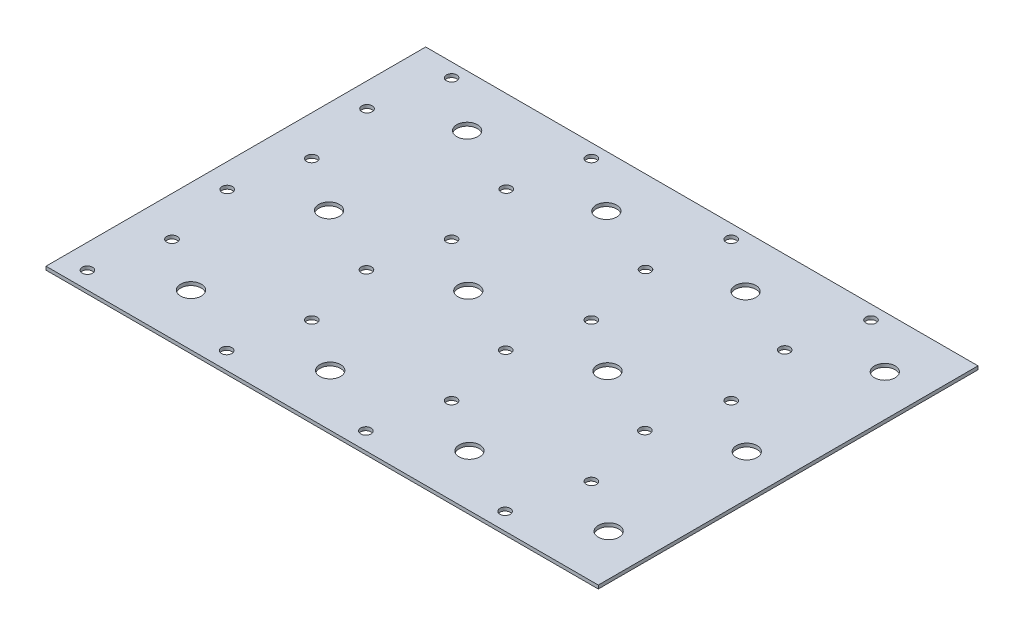
SolidWorks part; units mm, degrees
ref_plane "Front Plane" through (0, 0, 0) normal (0, 0, 1) x (1, 0, 0)
ref_plane "Top Plane" through (0, 0, 0) normal (0, 1, 0) x (1, 0, 0)
ref_plane "Right Plane" through (0, 0, 0) normal (1, 0, 0) x (0, 0, -1)
sketch "Sketch1" plane through (0, 0, 0) normal (0, 1, 0) x (1, 0, 0)
  line L1 (-80, -55) -> (80, -55)
  line L2 (-80, -55) -> (-80, 55)
  line L3 (-80, 55) -> (80, 55)
  line L4 (80, -55) -> (80, 55)
  line L5 (-80, -55) -> (80, 55) construction
  line L6 (-80, 55) -> (80, -55) construction
  point P0 (0, 0)
  dimension "D1" = 160
  dimension "D2" = 110
extrude "Boss-Extrude1" add sketch "Sketch1" along normal blind 1
sketch "Sketch2" plane through (0, 1, 0) normal (0, 1, 0) x (1, 0, 0)
  line L0 (-80, 55) -> (-80, -55) construction
  line L1 (80, 55) -> (-80, 55) construction
  line L2 (80, -55) -> (80, 55) construction
  line L3 (-80, -55) -> (80, -55) construction
  circle A0 centre (-53, 40) radius 3
  circle A1 centre (-12.6667, 40) radius 3
  circle A2 centre (27.6667, 40) radius 3
  circle A3 centre (68, 40) radius 3
  circle A4 centre (-12.6667, 0) radius 3
  circle A5 centre (27.6667, 0) radius 3
  circle A6 centre (68, 0) radius 3
  circle A7 centre (-12.6667, -40) radius 3
  circle A8 centre (27.6667, -40) radius 3
  circle A9 centre (68, -40) radius 3
  circle A10 centre (-53, 0) radius 3
  circle A11 centre (-53, -40) radius 3
  circle A12 centre (-68.5, 51) radius 1.5
  circle A13 centre (-28, 51) radius 1.5
  circle A14 centre (12.5, 51) radius 1.5
  circle A15 centre (53, 51) radius 1.5
  circle A16 centre (-28, 10.5) radius 1.5
  circle A17 centre (12.5, 10.5) radius 1.5
  circle A18 centre (53, 10.5) radius 1.5
  circle A19 centre (-28, -30) radius 1.5
  circle A20 centre (12.5, -30) radius 1.5
  circle A21 centre (53, -30) radius 1.5
  circle A22 centre (-68.5, 10.5) radius 1.5
  circle A23 centre (-68.5, -30) radius 1.5
  circle A24 centre (-73, 31) radius 1.5
  circle A25 centre (-32.6667, 31) radius 1.5
  circle A26 centre (7.6667, 31) radius 1.5
  circle A27 centre (48, 31) radius 1.5
  circle A28 centre (-32.6667, -9.5) radius 1.5
  circle A29 centre (7.6667, -9.5) radius 1.5
  circle A30 centre (48, -9.5) radius 1.5
  circle A31 centre (-32.6667, -50) radius 1.5
  circle A32 centre (7.6667, -50) radius 1.5
  circle A33 centre (48, -50) radius 1.5
  circle A34 centre (-73, -9.5) radius 1.5
  circle A35 centre (-73, -50) radius 1.5
  dimension "D1" = 6
  dimension "D8" = 3
  dimension "D15" = 3
  dimension "D2" = 27
  dimension "D3" = 15
  dimension "D6" = 12
  dimension "D7" = 15
  dimension "D9" = 11.5
  dimension "D12" = 27
  dimension "D13" = 4
  dimension "D14" = 25
  dimension "D16" = 24
  dimension "D17" = 7
  dimension "D20" = 32
  dimension "D21" = 5
  dimension "D4" = 4
  dimension "D5" = 3
  dimension "D10" = 4
  dimension "D11" = 3
  dimension "D18" = 4
  dimension "D19" = 3
extrude "Cut-Extrude1" cut sketch "Sketch2" against normal up to next (1 mm away)
ref_axis "Axis1" through (-12.6667, 0, 0) along (0, 1, 0)
ref_axis "Axis2" through (-53, 0, -40) along (0, 1, 0)
ref_axis "Axis3" through (-53, 0, 40) along (0, 1, 0)
ref_plane "Plane1" through (-6.2808, 0, -6.3331) normal (-0.7042, 0, -0.71) x (-0.71, 0, 0.7042)
ref_plane "Plane2" through (-6.2808, 0, 6.3331) normal (-0.7042, 0, 0.71) x (0.71, 0, 0.7042)
